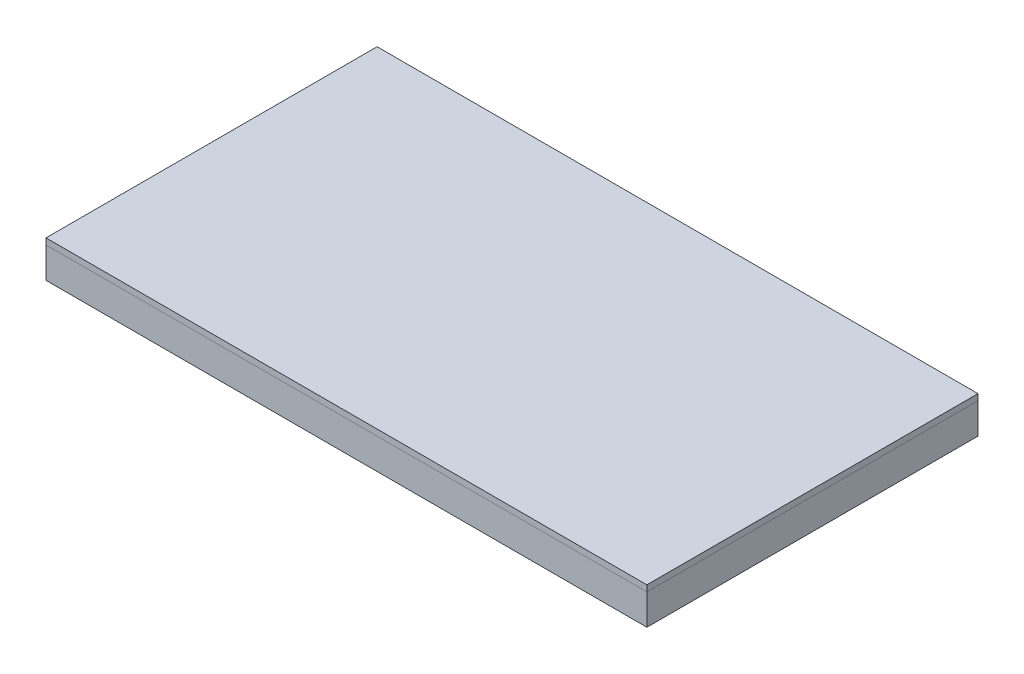
SolidWorks part; units mm, degrees
ref_plane "Front Plane" through (0, 0, 0) normal (0, 0, 1) x (1, 0, 0)
ref_plane "Top Plane" through (0, 0, 0) normal (0, 1, 0) x (1, 0, 0)
ref_plane "Right Plane" through (0, 0, 0) normal (1, 0, 0) x (0, 0, -1)
sketch "Sketch1" plane through (0, 0, 0) normal (0, 1, 0) x (1, 0, 0)
  line L1 (-490, -270) -> (490, -270)
  line L2 (-490, -270) -> (-490, 270)
  line L3 (-490, 270) -> (490, 270)
  line L4 (490, -270) -> (490, 270)
  line L5 (-490, -270) -> (490, 270) construction
  line L6 (-490, 270) -> (490, -270) construction
  line L7 (-480, -260) -> (480, -260)
  line L8 (-480, -260) -> (-480, 260)
  line L9 (-480, 260) -> (480, 260)
  line L10 (480, -260) -> (480, 260)
  line L11 (-480, -260) -> (480, 260) construction
  line L12 (-480, 260) -> (480, -260) construction
  point P0 (0, 0)
  point P6 (0, 0)
  dimension "D1" = 10
  dimension "D2" = 10
  dimension "D3" = 540
  dimension "D4" = 980
extrude "Boss-Extrude1" add sketch "Sketch1" along normal blind 10 contours L7 L10 L9 L8 | L1 L4 L3 L2 L10 L7 L8 L9 region at (-488.8811, 0, 0) region at (0, 0, 0)
extrude "Boss-Extrude2" add sketch "Sketch1<3>" against normal blind 50 separate body
sketch "Sketch1<3>" plane through (0, 0, 0) normal (0, 1, 0) x (1, 0, 0) same geometry as "Sketch1"
